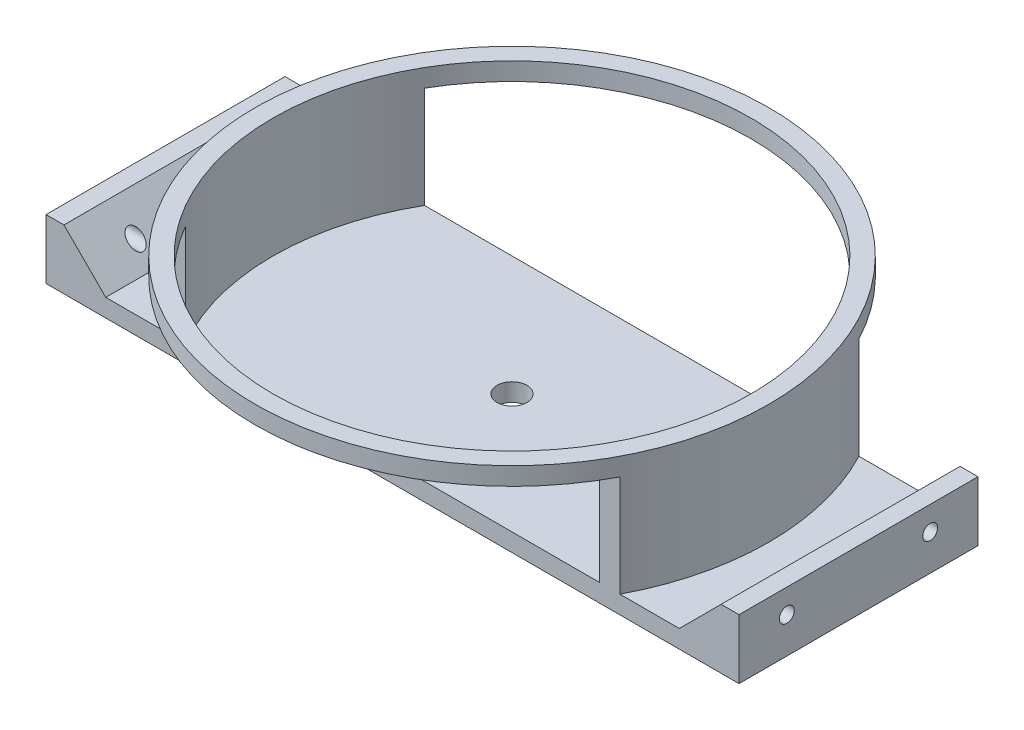
SolidWorks part; units mm, degrees
ref_plane "前视基准面" through (0, 0, 0) normal (0, 0, 1) x (1, 0, 0)
ref_plane "上视基准面" through (0, 0, 0) normal (0, 1, 0) x (1, 0, 0)
ref_plane "右视基准面" through (0, 0, 0) normal (1, 0, 0) x (0, 0, -1)
sketch "草图1" plane through (0, 0, 0) normal (0, 1, 0) x (1, 0, 0)
  line L1 (-58, 20) -> (58, 20)
  line L2 (-58, 20) -> (-58, -20)
  line L3 (-58, -20) -> (58, -20)
  line L4 (58, 20) -> (58, -20)
  line L5 (-58, 20) -> (58, -20) construction
  line L6 (-58, -20) -> (58, 20) construction
  point P0 (0, 0)
  dimension "D1" = 116
  dimension "D2" = 40
extrude "凸台-拉伸1" add sketch "草图1" along normal blind 3
sketch "草图2" plane through (0, 3, 0) normal (0, 1, 0) x (1, 0, 0)
  circle A0 centre (0, 0) radius 2.5
  dimension "D1" = 5
extrude "切除-拉伸1" cut sketch "草图2" against normal blind 3
sketch "草图3" plane through (0, 3, 0) normal (0, 1, 0) x (1, 0, 0)
  line L0 (-58, -20) -> (58, -20) construction
  line L1 (-58, 20) -> (-55, 20)
  line L2 (-58, 20) -> (-58, -20)
  line L3 (-58, -20) -> (-55, -20)
  line L4 (-55, 20) -> (-55, -20)
  line L5 (-58, 20) -> (-55, -20) construction
  line L6 (-58, -20) -> (-55, 20) construction
  line L8 (58, 20) -> (55, 20)
  line L9 (58, 20) -> (58, -20)
  line L10 (58, -20) -> (55, -20)
  line L11 (55, 20) -> (55, -20)
  line L12 (58, 20) -> (55, -20) construction
  line L13 (58, -20) -> (55, 20) construction
  point P4 (-56.5, 0)
  point P12 (56.5, 0)
  dimension "D1" = 3
  dimension "D2" = 3
extrude "凸台-拉伸2" add sketch "草图3" along normal blind 7
chamfer "倒角1" distance 7 angle 45 2 edges at (-55, 3, 0) (55, 3, 0)
sketch "草图4" plane through (-58, 0, 0) normal (-1, 0, 0) x (0, 0, 1)
  line L0 (-20, 10) -> (-20, 0) construction
  line L1 (20, 10) -> (20, 0) construction
  line L2 (-20, 10) -> (20, 10) construction
  circle A0 centre (-12, 6) radius 1.25
  circle A1 centre (12, 6) radius 1.25
  point P4 (0, 0)
  dimension "D1" = 2.5
  dimension "D2" = 2.5
  dimension "D3" = 8
  dimension "D4" = 8
  dimension "D5" = 4
extrude "切除-拉伸2" cut sketch "草图4" against normal through all both and the other way through all
ref_plane "基准面1" through (0, 23, 0) normal (0, 1, 0) x (1, 0, 0)
sketch "草图6" plane through (0, 23, 0) normal (0, 1, 0) x (1, 0, 0)
  circle A0 centre (0, 0) radius 40
  dimension "D1" = 80
extrude "拉伸-薄壁1" add sketch "草图6" against normal blind 3 separate body thin thin type one direction wall 3
sketch "草图7" plane through (0, 3, 0) normal (0, 1, 0) x (1, 0, 0)
  line L4 (-58, 20) -> (58, 20)
  line L5 (48, 20) -> (-48, 20) construction
  line L6 (-48, -20) -> (58, -20)
  line L7 (-58, 20) -> (-58, -20) construction
  line L8 (58, -20) -> (58, 20) construction
  circle A0 centre (0, 0) radius 43
  circle A1 centre (0, 0) radius 43
  circle A2 centre (0, 0) radius 40
  point P11 (57.5825, -20)
  point P12 (-55.9183, 20)
  point P15 (0, 0)
  point P18 (0, 0)
  dimension "D1" = 80
extrude "凸台-拉伸3" add sketch "草图7" along normal up to surface (17 mm away) contours A2 L4 A1 L6 | A2 L6 A1 L4 region at (-36.3534, 3, -19.5914) region at (41.3515, 3, -10.202) up to face at (0, 20, 40)
